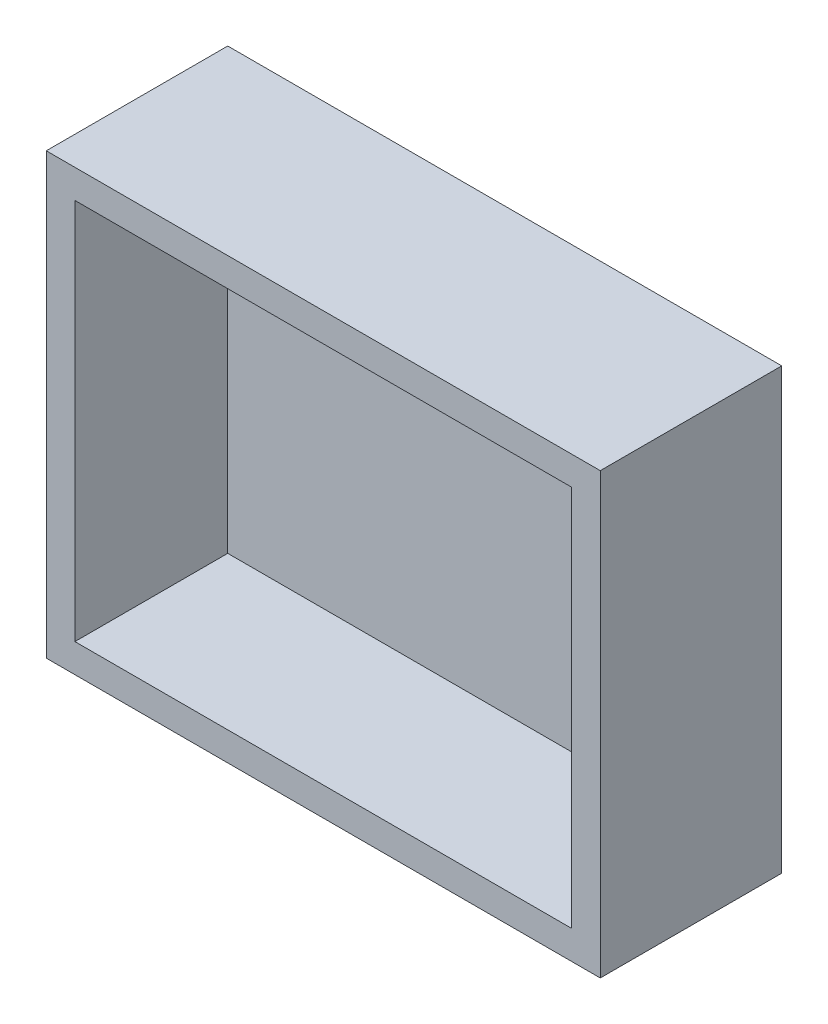
SolidWorks part; units mm, degrees
ref_plane "前视基准面" through (0, 0, 0) normal (0, 0, 1) x (1, 0, 0)
ref_plane "上视基准面" through (0, 0, 0) normal (0, 1, 0) x (1, 0, 0)
ref_plane "右视基准面" through (0, 0, 0) normal (1, 0, 0) x (0, 0, -1)
sketch "草图1" plane through (0, 0, 0) normal (0, 0, 1) x (1, 0, 0)
  line L0 (15, 15) -> (275, 15)
  line L1 (0, 0) -> (290, 0)
  line L2 (0, 0) -> (0, 230)
  line L3 (0, 230) -> (290, 230)
  line L4 (290, 0) -> (290, 230)
  line L5 (275, 15) -> (275, 215)
  line L6 (15, 215) -> (275, 215)
  line L7 (15, 15) -> (15, 215)
  dimension "D1" = 230
  dimension "D2" = 290
  dimension "D3" = 15
extrude "凸台-拉伸1" add sketch "草图1" along normal blind 80
extrude "凸台-拉伸2" add sketch "草图1<2>" against normal blind 15 contours L7 L0 L5 L6 | L1 L4 L3 L2 L0 L7 L6 L5 region at (145, 115, 0) region at (3.7014, 115, 0)
sketch "草图1<2>" plane through (0, 0, 0) normal (0, 0, 1) x (1, 0, 0) same geometry as "草图1"
